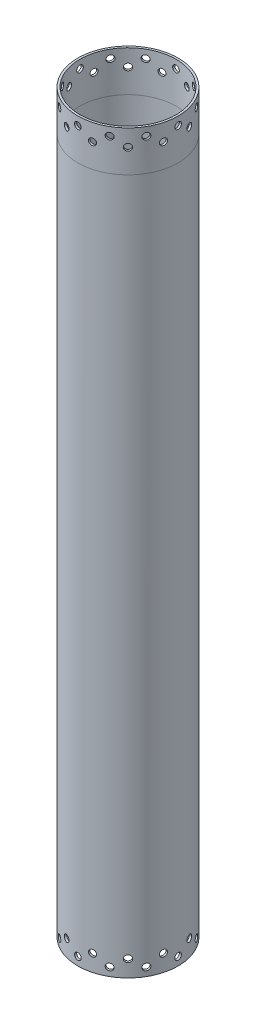
SolidWorks part; units mm, degrees
material "6061-T6 (SS)"
ref_plane "Front Plane" through (0, 0, 0) normal (0, 0, 1) x (1, 0, 0)
ref_plane "Top Plane" through (0, 0, 0) normal (0, 1, 0) x (1, 0, 0)
ref_plane "Right Plane" through (0, 0, 0) normal (1, 0, 0) x (0, 0, -1)
sketch "Sketch2" plane through (0, 0, 0) normal (0, 1, 0) x (1, 0, 0)
  circle A0 centre (0, 0) radius 76.2
  circle A1 centre (0, 0) radius 73.025
  dimension "D1" = 152.4
  dimension "D2" = 3.175
extrude "Boss-Extrude1" add sketch "Sketch2" along normal blind 1117.6
sketch "Sketch3" plane through (0, 0, 0) normal (0, 0, 1) x (1, 0, 0)
  line L0 (0, 1117.6) -> (0, 1104.9) construction
  line L1 (73.025, 1117.6) -> (-73.025, 1117.6) construction
  circle A0 centre (0, 1104.9) radius 5.0419
  dimension "D1" = 10.0838
  dimension "D2" = 12.7
extrude "Cut-Extrude1" cut sketch "Sketch3" against normal blind 1143
ref_plane "Plane1" through (-19.722, 0, 73.6035) normal (-0.2588, 0, 0.9659) x (0, -1, 0)
sketch "Sketch6" plane through (-19.722, 0, 73.6035) normal (-0.2588, 0, 0.9659) x (0, -1, 0)
  line L0 (-1117.6, 0) -> (-1092.2, 0) construction
  line L1 (-1117.6, 76.2) -> (-1117.6, -76.2) construction
  circle A0 centre (-1092.2, 0) radius 5.0419
  dimension "D1" = 10.0838
extrude "Cut-Extrude2" cut sketch "Sketch6" against normal blind 25.4
pattern_circular "CirPattern2" count 12 over 360 about axis through (0, 1117.6, 0) along (0, -1, 0) of "Cut-Extrude2", "Cut-Extrude1"
ref_plane "Plane2" through (0, 558.8, 0) normal (0, 1, 0) x (1, 0, 0)
mirror "Mirror1" about plane through (0, 558.8, 0) normal (0, 1, 0) of "CirPattern2"
ref_axis "Axis1" through (-69.9555, 1104.9, -40.3888) along (0.866, 0, 0.5)
ref_axis "Axis2" through (-40.3884, 1104.9, -69.9547) along (0.5, 0, 0.866)
ref_plane "Plane3" through (0, 1104.9, 0) normal (0, -1, 0) x (-1, 0, 0)
ref_axis "Axis3" through (-67.6049, 1092.2, -18.1147) along (-0.9659, 0, -0.2588)
ref_axis "Axis4" through (-47.674, 1092.2, -47.674) along (-0.7071, 0, -0.7071)
ref_plane "Plane4" through (0, 1092.2, 0) normal (0, 1, 0) x (1, 0, 0)
ref_plane "Plane5" through (0, 0, 0) normal (-0.5, 0.0045, 0.866) x (0.866, 0.0026, 0.5)
split line "Split Line2"
split line "Split Line3"
ref_axis "Axis5" through (47.674, 25.4, 47.674) along (0.7071, 0, 0.7071)
ref_axis "Axis6" through (67.6049, 25.4, 18.1147) along (0.9659, 0, 0.2588)
ref_axis "Axis7" through (69.9555, 12.7, 40.3888) along (-0.866, 0, -0.5)
ref_axis "Axis8" through (76.2, 12.7, 0) along (-1, 0, 0)
ref_plane "Plane7" through (0, 25.4, 0) normal (0, 1, 0) x (1, 0, 0)
ref_plane "Plane8" through (0, 12.7, 0) normal (0, 1, 0) x (1, 0, 0)
split line "Split Line4"
split line "Split Line5"
ref_plane "Plane9" through (0, 1055.878, 0) normal (0, 1, 0) x (1, 0, 0)
split line "Split Line6"
ref_plane "Plane10" through (0, 61.722, 0) normal (0, -1, 0) x (-1, 0, 0)
split line "Split Line11"
split line "Split Line12"
ref_axis "Axis9" through (0, 1055.878, 0) along (0, -1, 0)
equation "\"holeDia\"=0.397"
equation "\"D1@Sketch3\"=\"holeDia\""
equation "\"D1@Sketch6\"=\"holeDia\""
equation "\"numHoles\"=12"
equation "\"D1@CirPattern2\"=\"numHoles\""
equation "\"D1@Plane1\"=180/\"numHoles\""
